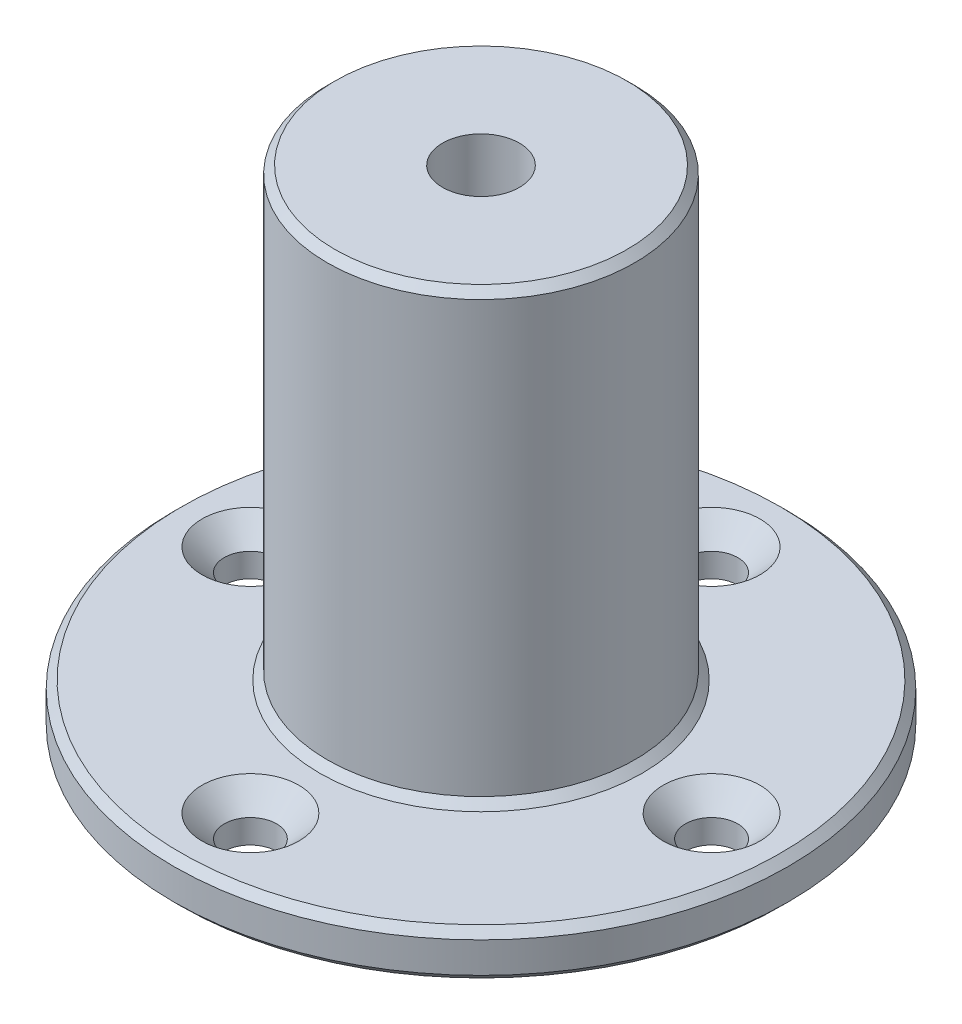
SolidWorks part; units mm, degrees
ref_plane "Front Plane" through (0, 0, 0) normal (0, 0, 1) x (1, 0, 0)
ref_plane "Top Plane" through (0, 0, 0) normal (0, 1, 0) x (1, 0, 0)
ref_plane "Right Plane" through (0, 0, 0) normal (1, 0, 0) x (0, 0, -1)
sketch "Sketch1" plane through (0, 0, 0) normal (0, 1, 0) x (1, 0, 0)
  circle A0 centre (0, 0) radius 10
  dimension "D1" = 20
extrude "Boss-Extrude1" add sketch "Sketch1" along normal blind 32 contours A0
sketch "Sketch2" plane through (0, 0, 0) normal (0, -1, 0) x (1, 0, 0)
  circle A0 centre (0, 0) radius 20
  dimension "D1" = 40
extrude "Boss-Extrude2" add sketch "Sketch2" against normal blind 3
hole_wizard "CSK for M3 Countersunk Flat Head Screw1" positions "Sketch4" profile "Sketch3" countersink size "M3" standard "ISO" end condition through all
sketch "Sketch4" plane through (0, 3, 0) normal (0, 1, 0) x (1, 0, 0)
  point P0 (0, 15)
  dimension "D1" = 15
sketch "Sketch3" plane through (0, 3, -15) normal (1, 0, 0) x (0, 0, 1)
  line L0 (0, 0) -> (0, 3)
  line L1 (0, 3) -> (1.7, 3)
  line L2 (1.7, 3) -> (1.7, 1.45)
  line L3 (1.7, 1.45) -> (3.15, 0)
  line L5 (3.15, 0) -> (0, 0)
  line L6 (-1.7, 1.45) -> (-3.15, 0) construction
  line L11 (0, -6.35) -> (0, 107.95) construction
  dimension "Thru Hole Dia." = 3.4
  dimension "Thru Hole Depth" = 3
  dimension "Near C'Sink Dia." = 6.3
  dimension "Near C'Sink Angle" = 90
pattern_circular "CirPattern1" count 4 over 360 about axis through (0, 3, 0) along (0, -1, 0) of "CSK for M3 Countersunk Flat Head Screw1"
hole_wizard "M6 Tapped Hole1" positions "Sketch6" profile "Sketch5" tap size "M6" standard "ISO"
sketch "Sketch6" plane through (0, 32, 0) normal (0, 1, 0) x (1, 0, 0)
  point P0 (0, 0)
sketch "Sketch5" plane through (0, 32, 0) normal (1, 0, 0) x (0, 0, 1)
  line L0 (0, 0) -> (0, 18.5022)
  line L1 (0, 18.5022) -> (2.5, 17)
  line L2 (2.5, 17) -> (2.5, 0)
  line L5 (2.5, 0) -> (0, 0)
  line L10 (0, 18.5022) -> (-2.5, 17) construction
  line L11 (0, -6.35) -> (0, 107.95) construction
  dimension "Tap Drill Dia." = 5
  dimension "Tap Drill Depth" = 17
  dimension "Drill Angle" = 118
chamfer "Chamfer1" distance 0.5 angle 45 4 edges at (0, 0, -20) (0, 3, -20) (0, 32, 10) (0, 3, -10)
